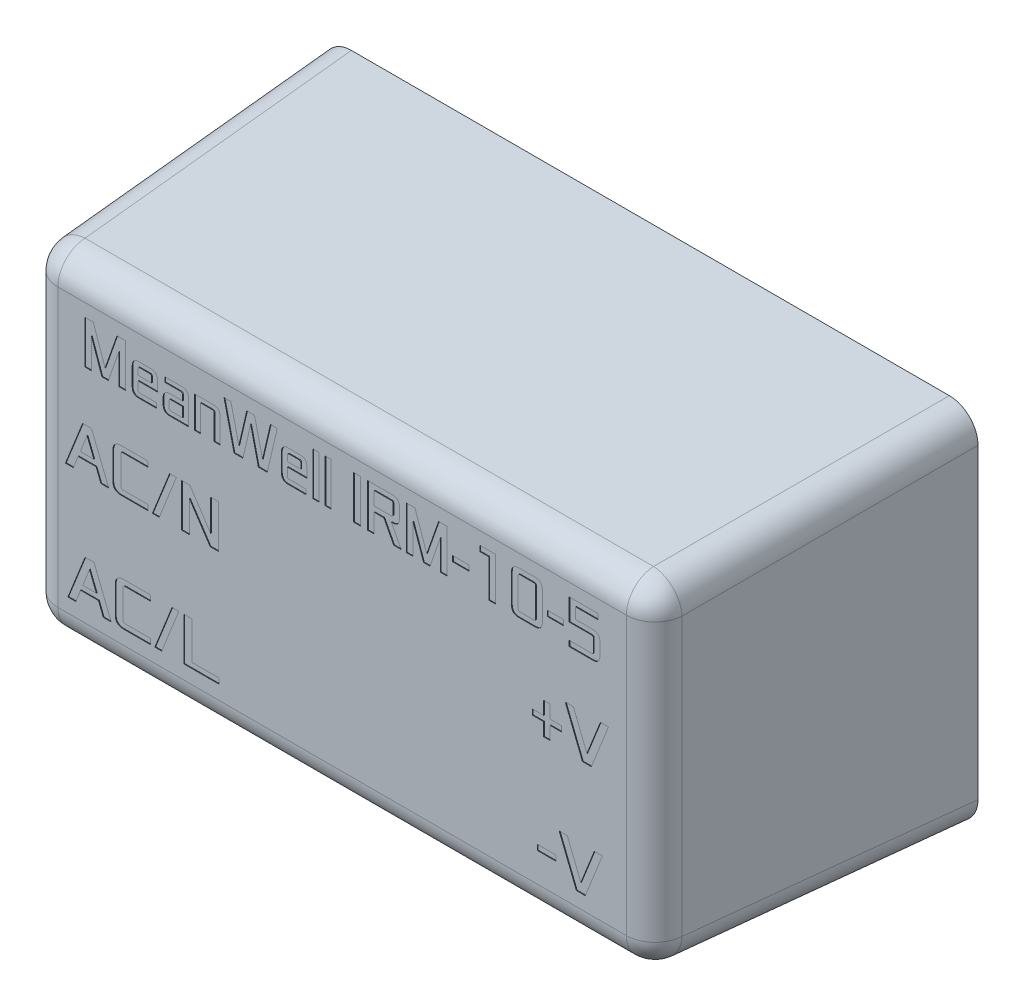
SolidWorks part; units mm, degrees
ref_plane "Plan de face" through (0, 0, 0) normal (0, 0, 1) x (1, 0, 0)
ref_plane "Plan de dessus" through (0, 0, 0) normal (0, 1, 0) x (1, 0, 0)
ref_plane "Plan de droite" through (0, 0, 0) normal (1, 0, 0) x (0, 0, -1)
sketch "Esquisse1" plane through (0, 0, 0) normal (0, 0, 1) x (1, 0, 0)
  line L1 (-22.85, 12.7) -> (22.85, 12.7)
  line L2 (-22.85, 12.7) -> (-22.85, -12.7)
  line L3 (-22.85, -12.7) -> (22.85, -12.7)
  line L4 (22.85, 12.7) -> (22.85, -12.7)
  line L5 (-22.85, 12.7) -> (22.85, -12.7) construction
  line L6 (-22.85, -12.7) -> (22.85, 12.7) construction
  point P0 (0, 0)
  dimension "D1" = 45.7
  dimension "D2" = 25.4
extrude "Boss.-Extru.1" add sketch "Esquisse1" along normal blind 21.5 draft 3
fillet "Congé1" radius 2 8 edges at (0, -11.5732, 21.5) (-21.7232, 0, 21.5) (0, 11.5732, 21.5) (21.7232, 0, 21.5) (-22.2866, -12.1366, 10.75) (-22.2866, 12.1366, 10.75) (22.2866, -12.1366, 10.75) (22.2866, 12.1366, 10.75)
sketch "Esquisse2" plane through (0, 0, 0) normal (0, 0, -1) x (-1, 0, 0)
  line L0 (19.25, -9.77) -> (14.2711, -9.77) construction
  line L2 (22.85, 10.7027) -> (22.85, -10.7027) construction
  line L3 (20.8527, -12.7) -> (-20.8527, -12.7) construction
  circle A0 centre (19.25, -9.25) radius 0.52
  dimension "D1" = 1.04
  dimension "D2" = 3.6
  dimension "D3" = 3.45
extrude "Boss.-Extru.2" add sketch "Esquisse2" along normal blind 3.5
pattern_linear "Répétition linéaire1" count 2 spacing 38.5 along (1, 0, 0) count 2 spacing 10.75 along (0, 1, 0) skipping (1, 1) of "Boss.-Extru.2"
pattern_linear "Répétition linéaire2" count 2 spacing 38.5 along (1, 0, 0) count 2 spacing 8 along (0, 1, 0) skipping (0, 1), (1, 0) of "Boss.-Extru.2"
chamfer "Chanfrein1" distance 0.5 angle 45 4 edges at (-19.77, -9.25, -3.5) (-19.77, 1.5, -3.5) (18.73, -9.25, -3.5) (18.73, -1.25, -3.5)
sketch "Esquisse4" plane through (0, 0, 21.5) normal (0, 0, 1) x (1, 0, 0)
  line L0 (-19.8253, -0.7) -> (-7.8253, -0.7) construction
  line L1 (-20.8527, -12.7) -> (20.8527, -12.7) construction
  line L2 (-19.8253, -8.7) -> (-7.8253, -8.7) construction
  line L3 (-19.8253, 9.6753) -> (-19.8253, -9.6753) construction
  line L4 (19.8253, -0.7) -> (11.8253, -0.7) construction
  line L5 (19.8253, -9.6753) -> (19.8253, 9.6753) construction
  line L6 (19.8253, -8.7) -> (11.8253, -8.7) construction
  text T0 "AC/L" font "Xolonium" height 3
  text T1 "AC/N" font "Xolonium" height 3
  text T2 "-V" font "Xolonium" height 3
  text T3 "+V" font "Xolonium" height 3
  point P14 (0, 0)
  dimension "D1" = 12
  dimension "D2" = 4
  dimension "D3" = 12
  dimension "D4" = 12
  dimension "D5" = 8
extrude "Enlèv. mat.-Extru.1" cut sketch "Esquisse4" against normal blind 0.05
sketch "Esquisse5" plane through (0, 0, 21.5) normal (0, 0, 1) x (1, 0, 0)
  line L0 (-19.8253, 5.7842) -> (19.8253, 5.7842) construction
  line L1 (-19.8253, 9.6753) -> (-19.8253, -9.6753) construction
  line L2 (19.8253, -9.6753) -> (19.8253, 9.6753) construction
  text T0 "MeanWell IRM-10-5" font "Xolonium" height 3
extrude "Enlèv. mat.-Extru.2" cut sketch "Esquisse5" against normal blind 0.05
